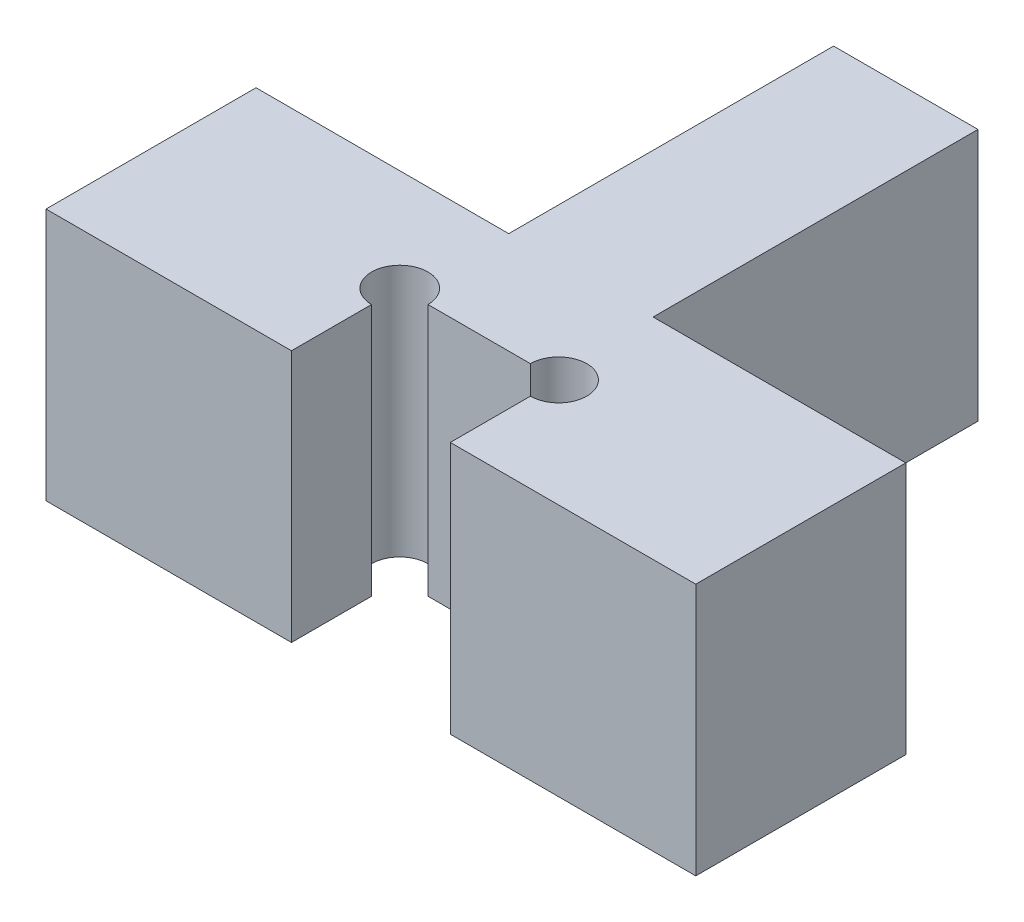
SolidWorks part; units mm, degrees
ref_plane "Front Plane" through (0, 0, 0) normal (0, 0, 1) x (1, 0, 0)
ref_plane "Top Plane" through (0, 0, 0) normal (0, 1, 0) x (1, 0, 0)
ref_plane "Right Plane" through (0, 0, 0) normal (1, 0, 0) x (0, 0, -1)
sketch "Sketch1" plane through (0, 0, 0) normal (0, 1, 0) x (1, 0, 0)
  line L0 (-4.5, -0.1642) -> (-1.1, -0.1642)
  line L1 (4.5, -0.1642) -> (4.5, 2.745)
  line L2 (4.5, 2.745) -> (1, 2.745)
  line L3 (1, 2.745) -> (1, 7.245)
  line L4 (1, 7.245) -> (-1, 7.245)
  line L5 (-1, 7.245) -> (-1, 2.745)
  line L6 (-1, 2.745) -> (-4.5, 2.745)
  line L7 (-4.5, 2.745) -> (-4.5, -0.1642)
  line L8 (1.1, -0.1642) -> (4.5, -0.1642)
  line L9 (-1.1, -0.1642) -> (1.1, -0.1642) construction
  line L10 (-1.1, -0.1642) -> (-1.1, 0.9454)
  line L11 (-0.7096, 1.3358) -> (0.7096, 1.3358)
  line L12 (1.1, -0.1642) -> (1.1, 0.9454)
  line L13 (-1.1, -0.1642) -> (1.1, -0.1642) construction
  line L14 (1, -1.6642) -> (1, 1.2358) construction
  line L15 (-1, 1.2358) -> (1, 1.2358) construction
  line L16 (10.5409, 5.745) -> (-46.7969, 5.745) construction
  line L17 (12.612, 2.745) -> (-45.868, 2.745) construction
  arc A0 (-0.7096, 1.3358) -> (-1.1, 0.9454) centre (-1.1, 1.3358) ccw
  arc A1 (1.1, 0.9454) -> (0.7096, 1.3358) centre (1.1, 1.3358) ccw
  point P4 (0, 0)
  point P25 (0, 7.245)
  dimension "D1" = 0.1
  dimension "D2" = 0.1
  dimension "D3" = 1.5
  dimension "D4" = 1.5
  dimension "D5" = 0.5
  dimension "D6" = 3.5
extrude "Boss-Extrude1" add sketch "Sketch1" along normal blind 3.5 contours L6 L7 L0 L10 A0 L11 A1 L12 L8 L1 L2 L3 L4 L5
